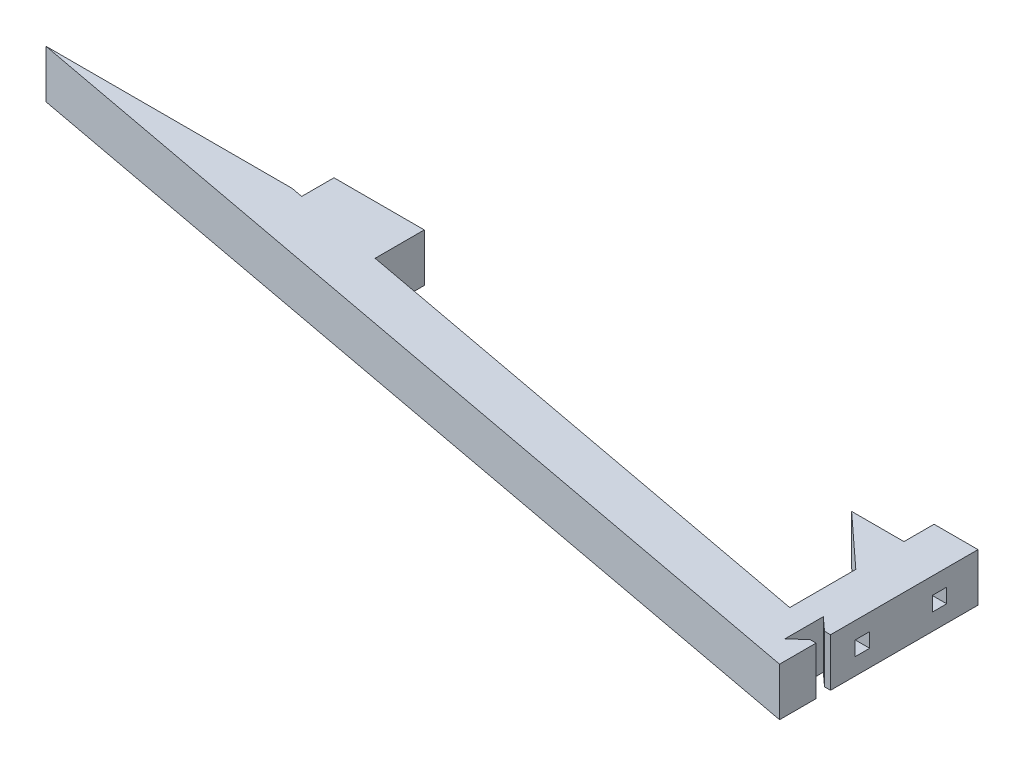
SolidWorks part; units mm, degrees
ref_plane "Přední rovina" through (0, 0, 0) normal (0, 0, 1) x (1, 0, 0)
ref_plane "Horní rovina" through (0, 0, 0) normal (0, 1, 0) x (1, 0, 0)
ref_plane "Pravá rovina" through (0, 0, 0) normal (1, 0, 0) x (0, 0, -1)
sketch "Skica2" plane through (0, 0, 0) normal (0, 1, 0) x (1, 0, 0)
  line L13 (0, 0) -> (0, -32.97)
  line L14 (0, -32.97) -> (-149.85, -5)
  line L15 (-149.85, -5) -> (-108.9746, -5)
  line L16 (-108.9746, -5) -> (-107, -5.3686)
  line L17 (-107, -5.3686) -> (-107, 0)
  line L18 (-107, 0) -> (-92, 0)
  line L19 (-92, 0) -> (-92, -8.1684)
  line L20 (-92, -8.1684) -> (-7.3, -23.9779)
  line L21 (-7.3, -23.9779) -> (-7.3, 0)
  line L22 (-7.3, 0) -> (0, 0)
  dimension "D1" = 32.97
  dimension "D2" = 149.85
  dimension "D3" = 7.5
  dimension "D4" = 15
  dimension "D5" = 7.3
  dimension "D6" = 5
  dimension "D7" = 7.5
  dimension "D8" = 84.7
extrude "Přidat vysunutím1" add sketch "Skica2" along normal blind 8
sketch "Skica3" plane through (0, 8, 0) normal (0, 1, 0) x (1, 0, 0)
  line L6 (0, -24.5) -> (-1, -24.5)
  line L7 (0, -32.97) -> (0, 0) construction
  line L8 (-1, -24.5) -> (-3.2, -22.5)
  line L9 (-3.2, -22.5) -> (-3.2, -28.9)
  line L10 (-3.2, -28.9) -> (-1, -26.9)
  line L11 (-1, -26.9) -> (0, -26.9)
  line L12 (0, -26.9) -> (0, -24.5)
  line L13 (0, 0) -> (-7.3, 0) construction
  dimension "D1" = 1
  dimension "D2" = 1
  dimension "D3" = 6.4
  dimension "D4" = 2.4
  dimension "D5" = 3.2
  dimension "D6" = 2
  dimension "40" = 22.5
extrude "Odebrat vysunutím1" cut sketch "Skica3" against normal through all
sketch "Skica5" plane through (0, 8, 0) normal (0, 1, 0) x (1, 0, 0)
  line L10 (0, -24.5) -> (0, 0) construction
  line L11 (0, -5) -> (-16, -5)
  line L12 (0, -5) -> (0, -13)
  line L13 (0, -13) -> (-16, -13)
  line L14 (-16, -5) -> (-16, -13)
  line L15 (0, 0) -> (-7.3, 0) construction
  dimension "D1" = 5
  dimension "D2" = 8
  dimension "D3" = 16
extrude "Přidat vysunutím2" add sketch "Skica5" against normal blind 8
sketch "Skica7" plane through (0, 0, 0) normal (0, -1, 0) x (1, 0, 0)
  line L3 (-16, 5) -> (-16, 13)
  line L4 (-16, 13) -> (-7.3, 13)
  line L5 (-7.3, 13) -> (-16, 5)
extrude "Odebrat vysunutím4" cut sketch "Skica7" against normal through all
sketch "Skica4" plane through (0, 0, 0) normal (1, 0, 0) x (0, 0, -1)
  line L0 (-24.5, 8) -> (0, 8) construction
  line L5 (-20.4, 5.2) -> (-18, 5.2)
  line L6 (-20.4, 5.2) -> (-20.4, 2.8)
  line L7 (-20.4, 2.8) -> (-18, 2.8)
  line L8 (-18, 5.2) -> (-18, 2.8)
  line L9 (-7.6, 5.2) -> (-5.2, 5.2)
  line L10 (-7.6, 5.2) -> (-7.6, 2.8)
  line L11 (-7.6, 2.8) -> (-5.2, 2.8)
  line L12 (-5.2, 5.2) -> (-5.2, 2.8)
  line L14 (0, 8) -> (0, 0) construction
  dimension "D3" = 2.4
  dimension "D4" = 2.4
  dimension "D5" = 2.4
  dimension "D6" = 2.4
  dimension "D7" = 2.8
  dimension "D8" = 2.8
  dimension "D10" = 5.2
  dimension "D11" = 10.4
extrude "Odebrat vysunutím2" cut sketch "Skica4" against normal blind 4.4
